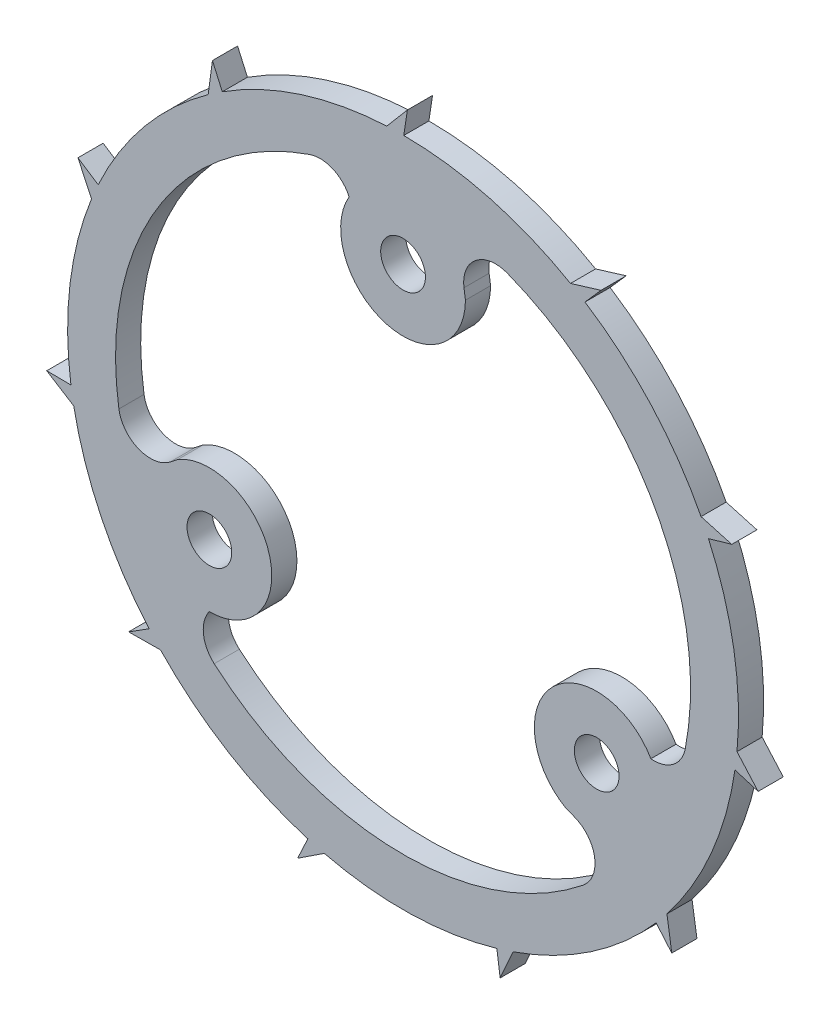
SolidWorks part; units mm, degrees
ref_plane "Front Plane" through (0, 0, 0) normal (0, 0, 1) x (1, 0, 0)
ref_plane "Top Plane" through (0, 0, 0) normal (0, 1, 0) x (1, 0, 0)
ref_plane "Right Plane" through (0, 0, 0) normal (1, 0, 0) x (0, 0, -1)
sketch "Sketch1" plane through (0, 0, 0) normal (0, 0, 1) x (1, 0, 0)
  line L0 (0, 0) -> (0, 17.78) construction
  line L1 (0, 17.78) -> (0, 20.32) construction
  line L2 (-4.2862, 20.275) -> (-4.2862, 22.4546)
  line L3 (4.9595, 17.78) -> (4.2862, 22.4546)
  line L8 (12.9182, -13.1851) -> (17.3031, -14.9393)
  line L9 (19.7017, -6.4255) -> (21.5894, -7.5153)
  line L12 (-17.8777, -4.5949) -> (-21.5894, -7.5153)
  line L13 (-15.4155, -13.8495) -> (-17.3031, -14.9393)
  circle A0 centre (0, 17.78) radius 1.778
  arc A1 (23.0969, 13.335) -> (-23.0969, 13.335) centre (0, 0) ccw
  arc A2 (-4.2862, 22.4546) -> (-19.7973, 11.43) centre (0, 0) ccw
  arc A3 (-4.2862, 20.275) -> (4.9595, 17.78) centre (0, 17.78) ccw
  arc A5 (19.7973, 11.43) -> (4.2862, 22.4546) centre (0, 0) ccw
  arc A6 (0, -26.67) -> (23.0969, 13.335) centre (0, 0) ccw
  arc A7 (0, -22.86) -> (17.3031, -14.9393) centre (0, 0) ccw
  arc A8 (19.7017, -6.4255) -> (12.9182, -13.1851) centre (15.3979, -8.89) ccw
  arc A9 (21.5894, -7.5153) -> (19.7973, 11.43) centre (0, 0) ccw
  circle A10 centre (15.3979, -8.89) radius 1.778
  arc A11 (-23.0969, 13.335) -> (0, -26.67) centre (0, 0) ccw
  arc A12 (-19.7973, 11.43) -> (-21.5894, -7.5153) centre (0, 0) ccw
  arc A13 (-15.4155, -13.8495) -> (-17.8777, -4.5949) centre (-15.3979, -8.89) ccw
  arc A14 (-17.3031, -14.9393) -> (0, -22.86) centre (0, 0) ccw
  circle A15 centre (-15.3979, -8.89) radius 1.778
  point P6 (0, 19.05)
  point P37 (0, 0)
  dimension "D1" = 17.78
  dimension "D2" = 3.556
  dimension "D3" = 53.34
  dimension "D4" = 45.72
  dimension "D7" = 3
extrude "Boss-Extrude1" add sketch "Sketch1" along normal blind 2
sketch "Sketch2" plane through (0, 0, 2) normal (0, 0, 1) x (1, 0, 0)
  line L0 (0.0563, 26.6699) -> (0.3464, 28.5729)
  line L1 (0.3464, 28.5729) -> (-1.2952, 26.6385)
  line L4 (-1.2952, 26.6385) -> (0.0563, 26.6699)
  circle A3 centre (0, 0) radius 28.575 construction
  circle A4 centre (0, 0) radius 26.67 construction
  point P2 (-1.8279, 28.5165)
  point P3 (-2.9738, 25.4)
  point P8 (-1.7094, 28.5238)
  point P10 (0.082, 25.3999)
  point P11 (-1.4701, 28.5372)
  point P12 (-3.8382, 28.316)
  point P13 (-3.6302, 28.3435)
  point P14 (-4.6669, 28.1913)
  point P15 (-4.6669, 24.9676)
  point P16 (-5.9976, 27.9385)
  point P17 (-1.5233, 25.3543)
  point P18 (0, 25.4)
  point P19 (-23.4524, 16.3254)
  point P20 (-27.9522, 5.9335)
  point P21 (1.997, 28.5051)
  point P22 (0.8081, 28.5636)
  point P23 (0, 28.575)
  point P24 (-0.7271, 25.3896)
  point P25 (-0.7375, 26.6598)
  point P26 (-1.2952, 26.6385)
  dimension "D1" = 57.15
  dimension "D2" = 7
fillet "Fillet1" radius 2.54 6 edges at (21.5894, -7.5153, 1) (17.3031, -14.9393, 1) (-17.3031, -14.9393, 1) (-21.5894, -7.5153, 1) (-4.2863, 22.4546, 1) (4.2862, 22.4546, 1)
extrude "Boss-Extrude2" add sketch "Sketch2" against normal up to surface (2 mm away) up to face at (1.778, 17.78, 0)
pattern_circular "CirPattern1" count 11 over 360 about axis through (0, 0, 2) along (0, 0, 1) of "Boss-Extrude2"
sketch "Sketch3" plane through (0, 0, 2) normal (0, 0, 1) x (1, 0, 0)
  line L0 (-8.3823, -27.3179) -> (-21.8208, -18.4495) construction
